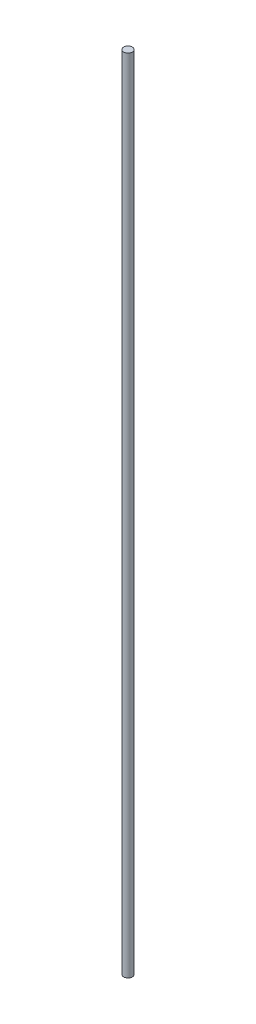
SolidWorks part; units mm, degrees
ref_plane "Front Plane" through (0, 0, 0) normal (0, 0, 1) x (1, 0, 0)
ref_plane "Top Plane" through (0, 0, 0) normal (0, 1, 0) x (1, 0, 0)
ref_plane "Right Plane" through (0, 0, 0) normal (1, 0, 0) x (0, 0, -1)
sketch "Sketch1" plane through (0, 0, 0) normal (0, 1, 0) x (1, 0, 0)
  circle A0 centre (0, 0) radius 5.08
extrude "Boss-Extrude1" add sketch "Sketch1" along normal blind 934.72
